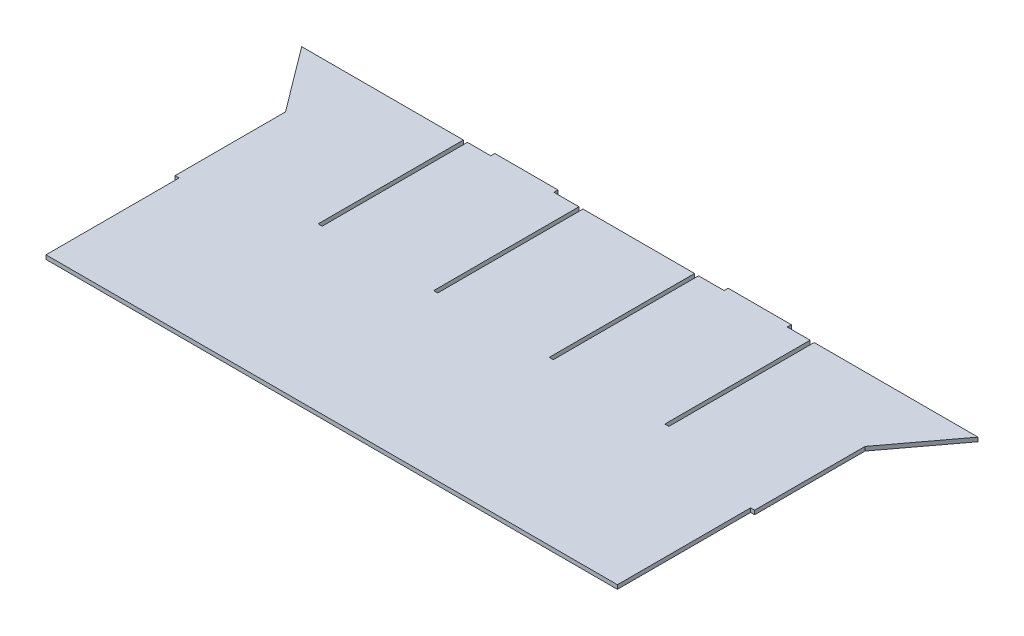
SolidWorks part; units mm, degrees
material "Custom Plastic"
ref_plane "X-Y Datum" through (0, 0, 0) normal (0, 0, 1) x (1, 0, 0)
ref_plane "X-Z Datum" through (0, 0, 0) normal (0, 1, 0) x (1, 0, 0)
ref_plane "Y-Z Datum" through (0, 0, 0) normal (1, 0, 0) x (0, 0, -1)
sketch "Sketch1" plane through (0, 0, 0) normal (0, 0, 1) x (1, 0, 0)
  line L1 (-227.966, -1.5875) -> (227.966, -1.5875)
  line L2 (-227.966, -1.5875) -> (-227.966, 1.5875)
  line L3 (-227.966, 1.5875) -> (227.966, 1.5875)
  line L4 (227.966, -1.5875) -> (227.966, 1.5875)
  line L5 (-227.966, -1.5875) -> (227.966, 1.5875) construction
  line L6 (-227.966, 1.5875) -> (227.966, -1.5875) construction
  point P0 (0, 0)
  dimension "D1" = 3.175
  dimension "D2" = 455.932
extrude "Boss-Extrude1" add sketch "Sketch1" along normal blind 242.425
sketch "Sketch2" plane through (0, 1.5875, 0) normal (0, 1, 0) x (1, 0, 0)
  line L0 (227.966, 0) -> (224.791, 0)
  line L1 (227.966, 0) -> (-227.966, 0) construction
  line L2 (224.791, 0) -> (137.161, 0)
  line L3 (137.161, 0) -> (133.986, 0)
  line L10 (133.986, 0) -> (137.161, 0)
  line L11 (133.986, 0) -> (133.986, -114.3)
  line L12 (133.986, -114.3) -> (137.161, -114.3)
  line L13 (137.161, 0) -> (137.161, -114.3)
  line M2 (227.966, 0) -> (-227.966, 0)
  dimension "D1" = 87.63
  dimension "D2" = 3.175
  dimension "D3" = 114.3
extrude "Cut-Extrude1" cut sketch "Sketch2" against normal through all contours L13 L11 L12 M2 region at (135.5735, 1.5875, 57.15)
pattern_linear "LPattern1" count 4 spacing 90.932 along (-1, 0, 0) of "Cut-Extrude1"
sketch "Sketch3" plane through (0, 0, 0) normal (0, 0, -1) x (-1, 0, 0)
  line L1 (-115.966, 1.5875) -> (-66.3072, 1.5875)
  line L2 (-115.966, 1.5875) -> (-115.966, -1.5875)
  line L3 (-115.966, -1.5875) -> (-66.3072, -1.5875)
  line L4 (-66.3072, 1.5875) -> (-66.3072, -1.5875)
  line L5 (67.5982, 1.5875) -> (117.257, 1.5875)
  line L6 (67.5982, 1.5875) -> (67.5982, -1.5875)
  line L7 (67.5982, -1.5875) -> (117.257, -1.5875)
  line L8 (117.257, 1.5875) -> (117.257, -1.5875)
extrude "Boss-Extrude2" add sketch "Sketch3" along normal blind 3.175
sketch "Sketch4" plane through (0, -1.5875, 0) normal (0, -1, 0) x (1, 0, 0)
  line L0 (-227.966, 0) -> (-266.066, 0)
  line L1 (-266.066, 0) -> (-227.966, 50.8)
  line L2 (-227.966, 242.425) -> (-227.966, 0) construction
  line L3 (-227.966, 50.8) -> (-227.966, 0)
  dimension "D1" = 38.1
  dimension "D2" = 50.8
extrude "Boss-Extrude3" add sketch "Sketch4" against normal blind 3.175
mirror "Mirror1" about plane through (0, 0, 0) normal (1, 0, 0) of "Boss-Extrude3"
sketch "Sketch5" plane through (0, -1.5875, 0) normal (0, -1, 0) x (1, 0, 0)
  line L1 (-227.966, 242.425) -> (-224.791, 242.425)
  line L2 (-227.966, 242.425) -> (-227.966, 137.65)
  line L3 (-227.966, 137.65) -> (-224.791, 137.65)
  line L4 (-224.791, 242.425) -> (-224.791, 137.65)
  dimension "D1" = 3.175
  dimension "D2" = 104.775
extrude "Cut-Extrude2" cut sketch "Sketch5" against normal blind 3.175
mirror "Mirror2" about plane through (0, 0, 0) normal (1, 0, 0) of "Cut-Extrude2"
